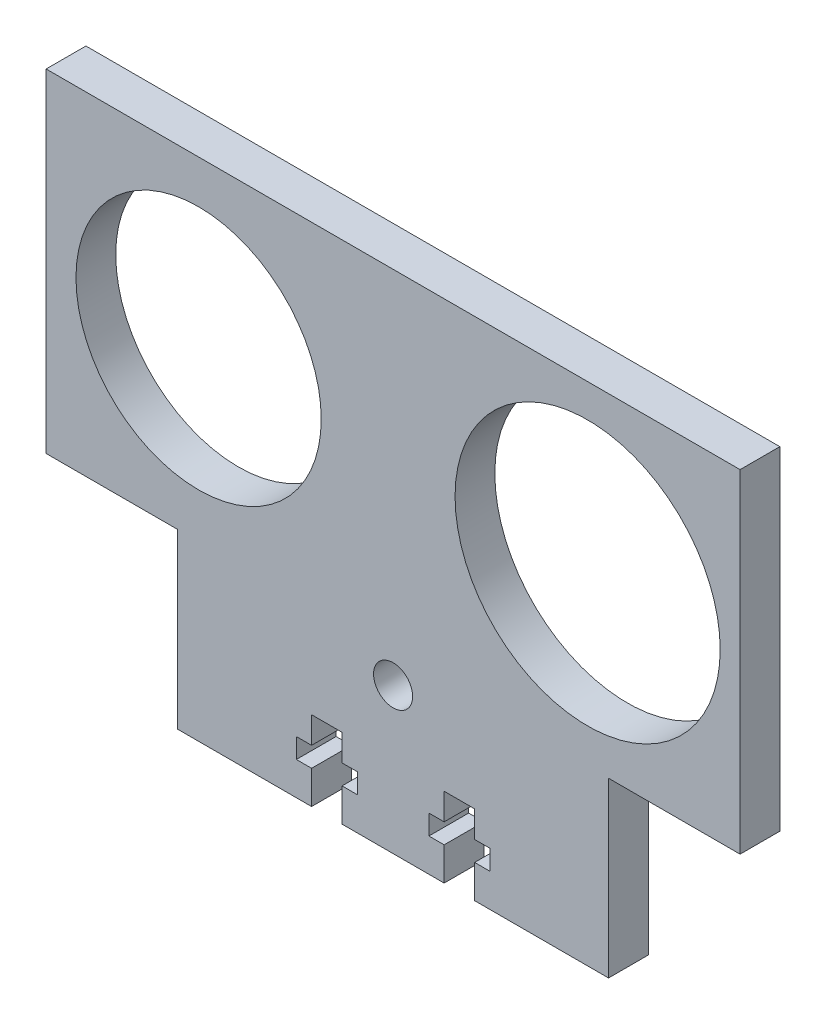
SolidWorks part; units mm, degrees
material "ABS"
ref_plane "Front Plane" through (0, 0, 0) normal (0, 0, 1) x (1, 0, 0)
ref_plane "Top Plane" through (0, 0, 0) normal (0, 1, 0) x (1, 0, 0)
ref_plane "Right Plane" through (0, 0, 0) normal (1, 0, 0) x (0, 0, -1)
sketch "Sketch1" plane through (0, 0, 0) normal (0, 0, 1) x (1, 0, 0)
  line L0 (0, 0) -> (-29.3449, 29.3449) construction
  line L1 (0, 0) -> (0, 54.3449) construction
  line L2 (-32.5, 4.1) -> (-32.5, -22)
  line L3 (-32.5, -22) -> (32.5, -22)
  line L4 (32.5, -22) -> (32.5, 4.1)
  line L5 (0, 0) -> (0, -22) construction
  line L6 (0, 0) -> (29.3449, 29.3449) construction
  line L10 (-32.5, 4.1) -> (-52.3449, 4.1)
  line L11 (-52.3449, 4.1) -> (-52.3449, 54.3449)
  line L12 (-52.3449, 54.3449) -> (52.3449, 54.3449)
  line L13 (52.3449, 54.3449) -> (52.3449, 4.1)
  line L14 (52.3449, 4.1) -> (32.5, 4.1)
  circle A0 centre (0, 0) radius 2.95
  circle A1 centre (29.3449, 29.3449) radius 20
  circle A2 centre (-29.3449, 29.3449) radius 18.5
  dimension "D1" = 5.9
  dimension "D9" = 37
  dimension "D11" = 40
  dimension "D2" = 41.5
  dimension "D4" = 45
  dimension "D5" = 22
  dimension "D6" = 65
  dimension "D3" = 23
  dimension "D7" = 25
  dimension "D8" = 26.1
  dimension "D10" = 45
extrude "Boss-Extrude1" add sketch "Sketch1" along normal blind 6
sketch "Sketch3" plane through (0, 0, 6) normal (0, 0, 1) x (1, 0, 0)
  line L0 (-32.5, -22) -> (32.5, -22) construction
  line L1 (-12.3, -22) -> (-7.7, -22)
  line L2 (-12.3, -22) -> (-12.3, -17)
  line L3 (-12.3, -10) -> (-7.7, -10)
  line L4 (-7.7, -22) -> (-7.7, -17)
  line L5 (0, 0) -> (0, -22) construction
  line L6 (-7.7, -14) -> (-5.4, -14)
  line L7 (-14.6, -14) -> (-12.3, -14)
  line L8 (-14.6, -14) -> (-14.6, -17)
  line L9 (-14.6, -17) -> (-12.3, -17)
  line L10 (-5.4, -14) -> (-5.4, -17)
  line L11 (-12.3, -14) -> (-12.3, -10)
  line L12 (-7.7, -17) -> (-5.4, -17)
  line L13 (-7.7, -14) -> (-7.7, -10)
  line L14 (7.7, -14) -> (7.7, -10)
  line L15 (7.7, -17) -> (5.4, -17)
  line L16 (12.3, -14) -> (12.3, -10)
  line L17 (5.4, -14) -> (5.4, -17)
  line L18 (14.6, -17) -> (12.3, -17)
  line L19 (14.6, -14) -> (14.6, -17)
  line L20 (14.6, -14) -> (12.3, -14)
  line L21 (7.7, -14) -> (5.4, -14)
  line L22 (7.7, -22) -> (7.7, -17)
  line L23 (12.3, -10) -> (7.7, -10)
  line L24 (12.3, -22) -> (12.3, -17)
  line L25 (12.3, -22) -> (7.7, -22)
  point P6 (-10, -10)
  point P18 (-13.45, -17)
  dimension "D1" = 4.6
  dimension "D2" = 10
  dimension "D3" = 12
  dimension "D4" = 9.2
  dimension "D5" = 3
  dimension "D6" = 5
extrude "Cut-Extrude2" cut sketch "Sketch3" against normal through all
equation "\"smallPulleyTeeth\"= 15"
equation "\"largePulleyTeeth\"= 30"
equation "\"eighthThick\"= 2.9mm"
equation "\"sixteenthThick\"= 1.7mm"
equation "\"quarterThick\"=6.0mm"
equation "\"OD\"= 145mm"
equation "\"puckAngle\"= 60.5deg"
equation "\"puckDiam\"= 76.5mm"
equation "\"axlePress\"= 5.9mm"
equation "\"D1@Sketch1\"=\"axlePress\""
equation "\"D1@Boss-Extrude1\"=\"quarterThick\""
equation "\"press\"= 0.2mm"
equation "\"wheelClear\"= 0.3mm"
equation "\"10-32clear\"= 4.8mm"
equation "\"D1@Sketch3\"=\"10-32clear\"-\"press\""
equation "\"6-32clear\"= 3.3mm"
equation "\"8-32clear\"= 4.0mm"
equation "\"wheelHeight\"= 22mm"
equation "\"D5@Sketch1\"=\"wheelHeight\""
equation "\"D8@Sketch1\"=\"eighthThick\"*9"
equation "\"4-40clear\"= 3.0mm"
equation "\"wheelWell\"= 65mm"
equation "\"D6@Sketch1\"=\"wheelWell\""
